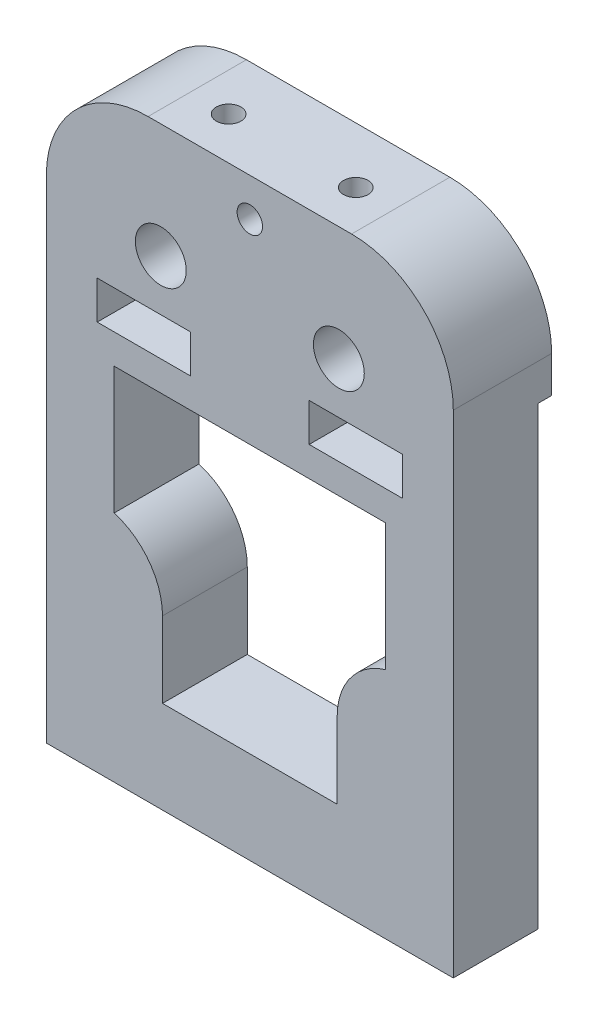
SolidWorks part; units mm, degrees
ref_plane "Front Plane" through (0, 0, 0) normal (0, 0, 1) x (1, 0, 0)
ref_plane "Top Plane" through (0, 0, 0) normal (0, 1, 0) x (1, 0, 0)
ref_plane "Right Plane" through (0, 0, 0) normal (1, 0, 0) x (0, 0, -1)
sketch "Sketch1" plane through (0, 0, 0) normal (0, 0, 1) x (1, 0, 0)
  line L1 (0, 0) -> (48, 0)
  line L2 (0, 0) -> (0, -70)
  line L3 (0, -70) -> (48, -70)
  line L4 (48, 0) -> (48, -70)
  dimension "D1" = 48
  dimension "D2" = 70
extrude "Boss-Extrude1" add sketch "Sketch1" along normal blind 10
sketch "Sketch2" plane through (0, 0, 10) normal (0, 0, 1) x (1, 0, 0)
  line L0 (0, 0) -> (0, -70) construction
  line L1 (48, 0) -> (0, 0) construction
  circle A0 centre (13.5, -13.5) radius 3
  circle A1 centre (34.5, -13.5) radius 3
  dimension "D1" = 6
  dimension "D2" = 6
  dimension "D3" = 21
  dimension "D4" = 13.5
  dimension "D5" = 13.5
  dimension "D6" = 13.5
extrude "Cut-Extrude1" cut sketch "Sketch2" against normal through all
sketch "Sketch3" plane through (0, 0, 10) normal (0, 0, 1) x (1, 0, 0)
  line L0 (0, 0) -> (0, -70) construction
  line L1 (13.7, -38.5) -> (34.3, -38.5)
  line L2 (13.7, -38.5) -> (13.7, -59.1)
  line L3 (13.7, -59.1) -> (34.3, -59.1)
  line L4 (34.3, -38.5) -> (34.3, -59.1)
  circle A0 centre (13.5, -13.5) radius 3 construction
  dimension "D1" = 20.6
  dimension "D2" = 20.6
  dimension "D3" = 13.7
  dimension "D4" = 25
extrude "Cut-Extrude2" cut sketch "Sketch3" against normal through all
fillet "Fillet1" radius 12 2 edges at (0, 0, 5) (48, 0, 5)
ref_plane "打印面" through (0, 0, -10) normal (0, 0, 1) x (1, 0, 0)
sketch "Sketch4" plane through (0, 0, 0) normal (0, 0, -1) x (-1, 0, 0)
  line L0 (-36, 0) -> (-12, 0) construction
  circle A0 centre (-24, -4.5) radius 1.5
  dimension "D1" = 3
  dimension "D2" = 4.5
extrude "Cut-Extrude3" cut sketch "Sketch4" against normal through all
sketch "Sketch5" plane through (0, 0, 0) normal (0, 1, 0) x (1, 0, 0)
  line L0 (36, -10) -> (12, -10) construction
  circle A0 centre (16.5, -5) radius 1.45
  circle A1 centre (31.5, -5) radius 1.45
  point P6 (24, -10)
  dimension "D1" = 2.9
  dimension "D3" = 5
  dimension "D4" = 7.5
extrude "Cut-Extrude4" cut sketch "Sketch5" against normal blind 10
sketch "Sketch7" plane through (0, 0, 0) normal (0, 0, -1) x (-1, 0, 0)
  line L0 (-48, -70) -> (-48, -12) construction
  line L1 (-42, -19.5) -> (-31, -19.5)
  line L2 (-42, -19.5) -> (-42, -24)
  line L3 (-42, -24) -> (-31, -24)
  line L4 (-31, -19.5) -> (-31, -24)
  line L5 (-24, 0) -> (-24, -28.6841) construction
  line L6 (-36, 0) -> (-12, 0) construction
  line L7 (-34.3, -38.5) -> (-13.7, -38.5) construction
  line L8 (-17, -19.5) -> (-17, -24)
  line L9 (-6, -24) -> (-17, -24)
  line L10 (-6, -19.5) -> (-6, -24)
  line L11 (-6, -19.5) -> (-17, -19.5)
  dimension "D1" = 4.5
  dimension "D2" = 11
  dimension "D3" = 6
  dimension "D4" = 14.5
extrude "Cut-Extrude5" cut sketch "Sketch7" against normal through all both and the other way through all
sketch "Sketch11" plane through (0, 0, 0) normal (0, 0, -1) x (-1, 0, 0)
  line L0 (-31, -24) -> (-42, -24) construction
  line L1 (-40, -27.5) -> (-8, -27.5)
  line L2 (-40, -27.5) -> (-40, -42.5)
  line L3 (-40, -42.5) -> (-8, -42.5)
  line L4 (-8, -27.5) -> (-8, -42.5)
  dimension "D1" = 15
  dimension "D2" = 3.5
  dimension "D3" = 2
  dimension "D4" = 2
extrude "Cut-Extrude6" cut sketch "Sketch11" against normal through all
sketch "Sketch12" plane through (0, -24, 0) normal (0, 1, 0) x (1, 0, 0)
  line L0 (31, 0) -> (42, 0) construction
  line L1 (6, 0) -> (17, 0) construction
  circle A0 centre (36.5, -3) radius 1.5
  circle A1 centre (11.5, -3) radius 1.5
  dimension "D1" = 3
  dimension "D3" = 3
extrude "Cut-Extrude7" cut sketch "Sketch12" against normal blind 5 and the other way blind 8
sketch "Sketch13" plane through (0, 0, 0) normal (0, 0, -1) x (-1, 0, 0)
  line L0 (-48, -70) -> (-48, -12) construction
  line L1 (-48, -16.3) -> (0, -16.3)
  line L2 (-48, -16.3) -> (-48, 0)
  line L3 (-48, 0) -> (0, 0)
  line L4 (0, -16.3) -> (0, 0)
  circle A0 centre (-34.5, -13.5) radius 3
  circle A1 centre (-13.5, -13.5) radius 3
  circle M10 centre (-24, -4.5) radius 1.5
  circle M19 centre (-34.5, -13.5) radius 3
  circle M20 centre (-13.5, -13.5) radius 3
  line M21 (0, -70) -> (0, -12)
  arc M22 (0, -12) -> (-12, 0) centre (-12, -12) ccw
  line M23 (-12, 0) -> (-36, 0)
  arc M24 (-36, 0) -> (-48, -12) centre (-36, -12) ccw
  line M25 (-48, -12) -> (-48, -70)
  dimension "D1" = 16.3
extrude "Boss-Extrude4" add sketch "Sketch13" along normal blind 1.6 contours L1 M25 M19 M20 M21 M22 M23 M24 M10 region at (24, -8.2505, 0)
fillet "Fillet2" radius 8 2 edges at (13.7, -42.5, 5) (34.3, -42.5, 5)
sketch "Sketch14" plane through (0, 0, 0) normal (0, 0, -1) x (-1, 0, 0)
  line L1 (-38.639, -48.7499) -> (-36.3361, -48.7499)
  line L2 (-38.639, -48.7499) -> (-38.639, -41.791)
  line L3 (-38.639, -41.791) -> (-36.3361, -41.791)
  line L4 (-36.3361, -48.7499) -> (-36.3361, -41.791)
equation "\"D3@Sketch3\"=(\"D1@Sketch1\"-\"D1@Sketch3\")/2"
equation "\"滑动-垂直孔\"= 0.6"
equation "\"滑动-水平孔\"= 0.3"
equation "\"松动-垂直孔\"= 0.3"
equation "\"松动-水平孔\"= 0.1"
equation "\"正常-垂直孔\"= 0.15"
equation "\"正常-水平孔\"= 0"
equation "\"紧缩-垂直孔\"= 0"
equation "\"紧缩-水平孔\"= - 0.1"
equation "\"D2@Sketch2\"=\"紧缩-垂直孔\"+6"
equation "\"D1@Sketch2\"=\"D2@Sketch2\""
equation "\"D2@Sketch3\"=\"滑动-垂直孔\"+20"
equation "\"D1@Sketch3\"=\"D2@Sketch3\""
equation "\"D4@Sketch3\"=19/2+20-6+1.5"
equation "\"D1@Sketch4\"=\"紧缩-垂直孔\"+3"
equation "\"D1@Sketch5\"=\"紧缩-水平孔\"+3"
equation "\"D3@Sketch5\"=\"D1@Boss-Extrude1\"/2"
equation "\"D4@Sketch5\"=7.5"
equation "\"D1@Sketch12\"=\"正常-水平孔\"+3"
equation "\"D3@Sketch12\"=\"D1@Sketch12\""
